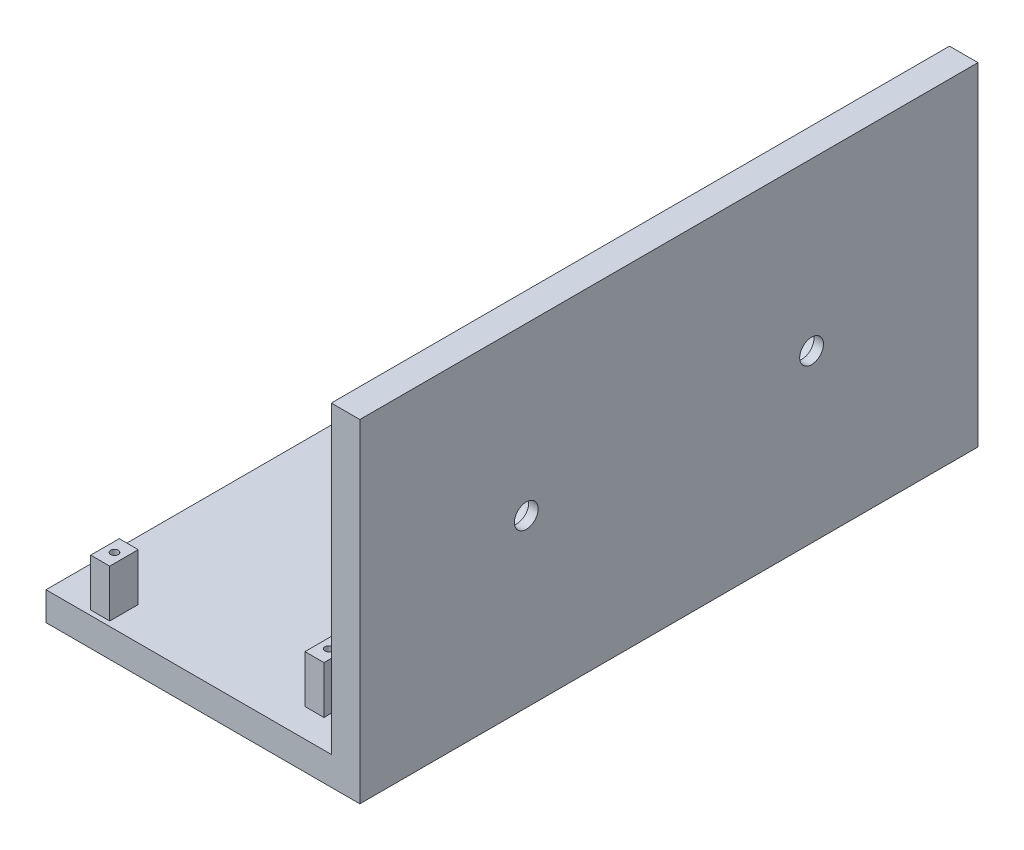
SolidWorks part; units mm, degrees
ref_plane "Front Plane" through (0, 0, 0) normal (0, 0, 1) x (1, 0, 0)
ref_plane "Top Plane" through (0, 0, 0) normal (0, 1, 0) x (1, 0, 0)
ref_plane "Right Plane" through (0, 0, 0) normal (1, 0, 0) x (0, 0, -1)
sketch "Sketch1" plane through (0, 0, 0) normal (0, 0, 1) x (1, 0, 0)
  line L0 (0, 0) -> (33, 0)
  line L1 (33, 0) -> (33, 35)
  line L2 (33, 35) -> (30, 35)
  line L3 (30, 35) -> (30, 3)
  line L4 (30, 3) -> (0, 3)
  line L5 (0, 3) -> (0, 0)
  dimension "D1" = 35
  dimension "D2" = 3
  dimension "D3" = 32
  dimension "D4" = 30
  dimension "D5" = 3
extrude "Boss-Extrude1" add sketch "Sketch1" along normal blind 65
sketch "Sketch2" plane through (0, 3, 0) normal (0, 1, 0) x (1, 0, 0)
  line L0 (0, -32.5) -> (30, -32.5)
  line L1 (0, -65) -> (0, 0) construction
  line L2 (30, -65) -> (30, 0) construction
  line L3 (15, -32.5) -> (15, -63)
  line L4 (15, -60.52) -> (25.25, -60.52)
  line L5 (26.25, -2.98) -> (24.25, -5.98) construction
  line L6 (26.25, -62.02) -> (24.25, -62.02)
  line L7 (26.25, -62.02) -> (26.25, -59.02)
  line L8 (26.25, -59.02) -> (24.25, -59.02)
  line L9 (24.25, -62.02) -> (24.25, -59.02)
  line L10 (26.25, -62.02) -> (24.25, -59.02) construction
  line L11 (26.25, -59.02) -> (24.25, -62.02) construction
  line L12 (26.25, -5.98) -> (24.25, -2.98) construction
  line L13 (26.25, -5.98) -> (24.25, -5.98)
  line L14 (24.25, -2.98) -> (24.25, -5.98)
  line L15 (26.25, -2.98) -> (24.25, -2.98)
  line L16 (26.25, -2.98) -> (26.25, -5.98)
  line L17 (15, -32.5) -> (15, -5.1)
  line L18 (15, -5.1) -> (6, -5.1)
  line L19 (15, -63) -> (5.2, -63)
  line L20 (7, -6.6) -> (5, -6.6)
  line L21 (7, -6.6) -> (7, -3.6)
  line L22 (7, -3.6) -> (5, -3.6)
  line L23 (5, -6.6) -> (5, -3.6)
  line L24 (7, -6.6) -> (5, -3.6) construction
  line L25 (7, -3.6) -> (5, -6.6) construction
  line L27 (6.2, -64.5) -> (4.2, -64.5)
  line L28 (6.2, -64.5) -> (6.2, -61.5)
  line L29 (6.2, -61.5) -> (4.2, -61.5)
  line L30 (4.2, -64.5) -> (4.2, -61.5)
  line L31 (6.2, -64.5) -> (4.2, -61.5) construction
  line L32 (6.2, -61.5) -> (4.2, -64.5) construction
  circle A0 centre (25.25, -60.52) radius 0.4
  circle A1 centre (25.25, -4.48) radius 0.4
  circle A2 centre (6, -5.1) radius 0.4
  circle A3 centre (5.2, -63) radius 0.4
  point P13 (25.25, -4.48)
  line M4 (30, -65) -> (30, 0)
  dimension "D5" = 0.8
  dimension "D10" = 0.8
  dimension "D15" = 0.8
  dimension "D1" = 28.02
  dimension "D2" = 10.25
  dimension "D3" = 2
  dimension "D4" = 3
  dimension "D6" = 27.4
  dimension "D7" = 9
  dimension "D8" = 2
  dimension "D9" = 3
  dimension "D11" = 9.8
  dimension "D12" = 30.5
  dimension "D13" = 2
  dimension "D14" = 3
extrude "Boss-Extrude2" add sketch "Sketch2" along normal blind 5 contours A0 L9 L6 L8 M4 | L15 L14 L13 A1 M4 | A3 L28 L29 L30 L27 | A2 L21 L22 L23 L20 region at (24.2861, 3, 59.77) region at (6.1639, 3, 63.75) region at (6.9639, 3, 5.85) region at (25.25, 3, 5.9439)
sketch "Sketch3" plane through (0, 3, 0) normal (0, 1, 0) x (1, 0, 0)
  line L0 (30, -32.5) -> (0, -32.5)
  line L1 (30, -65) -> (30, 0) construction
  line L2 (0, -65) -> (0, 0) construction
  line L3 (0, -32.5) -> (15, -32.5)
  line L4 (15, -32.5) -> (15, -17)
  line L5 (15, -17) -> (18.19, -17)
  line L6 (30, -21.5743) -> (30, -12.3727)
  line L8 (30, -21.5743) -> (13.5, -21.5743)
  line L9 (13.5, -21.5743) -> (13.5, -12.3727)
  line L10 (13.5, -12.3727) -> (30, -12.3727)
  dimension "D1" = 15.5
  dimension "D2" = 3.19
  dimension "D3" = 16.5
  dimension "D4" = 9.2015
extrude "Cut-Extrude2" cut sketch "Sketch3" against normal up to next contours L10 L9 L8 region at (21.75, 3, 16.9735)
sketch "Sketch4" plane through (33, 0, 0) normal (1, 0, 0) x (0, 0, -1)
  line L0 (-32.5, 35) -> (-32.5, 0)
  line L1 (-65, 35) -> (0, 35) construction
  line L2 (-65, 0) -> (0, 0) construction
  line L3 (-32.5, 17.5) -> (-47.5, 17.5)
  circle A0 centre (-47.5, 17.5) radius 1.25
  circle A3 centre (-17.5, 17.5) radius 1.25
  dimension "D2" = 2.5
  dimension "D1" = 15
extrude "Cut-Extrude3" cut sketch "Sketch4" against normal up to next contours A0 | A3 region at (33, 17.5, 48.7146) region at (33, 17.5, 17.5)
sketch "Sketch8" plane through (30, 0, 0) normal (-1, 0, 0) x (0, 0, 1)
  line L0 (32.5, 35) -> (32.5, 3)
  line L1 (65, 35) -> (0, 35) construction
  line L2 (65, 3) -> (21.5743, 3) construction
  circle A0 centre (17.5, 17.5) radius 2.5
  circle A1 centre (47.5, 17.5) radius 2.5
  dimension "D1" = 5
extrude "Cut-Extrude6" cut sketch "Sketch8" against normal blind 2 contours A0 | A1
